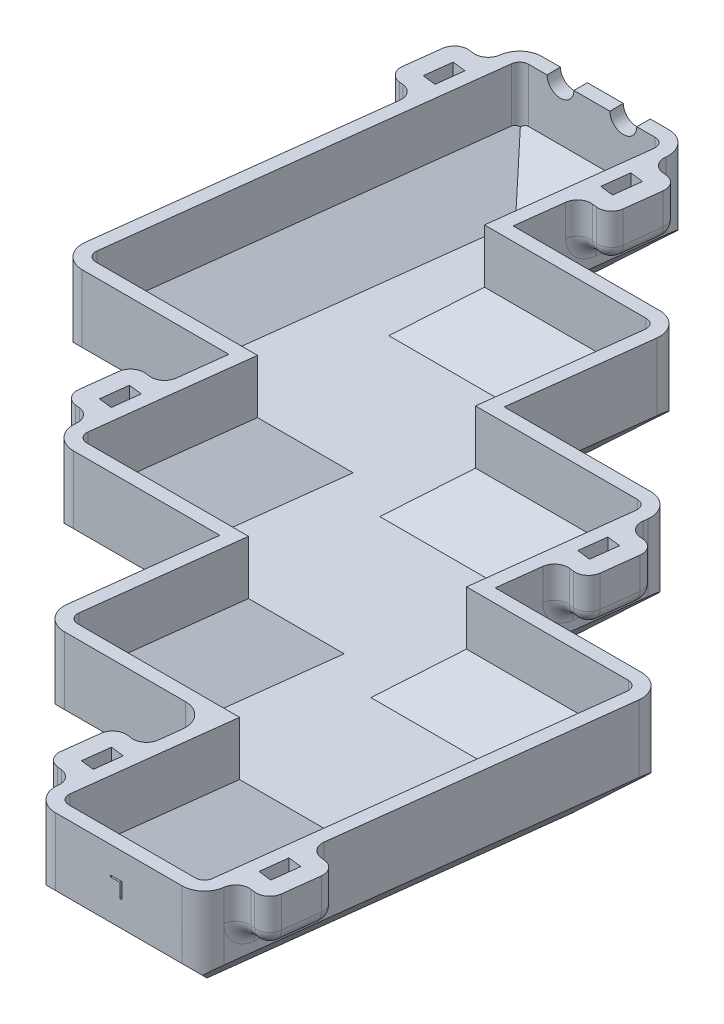
SolidWorks part; units mm, degrees
ref_plane "Front Plane" through (0, 0, 0) normal (0, 0, 1) x (1, 0, 0)
ref_plane "Top Plane" through (0, 0, 0) normal (0, 1, 0) x (1, 0, 0)
ref_plane "Right Plane" through (0, 0, 0) normal (1, 0, 0) x (0, 0, -1)
sketch "Sketch1" plane through (0, 0, 0) normal (0, 1, 0) x (1, 0, 0)
  line L12 (-13.5006, 46.1566) -> (24.7822, 46.1566)
  line L17 (-13.5006, 46.1566) -> (-24.7822, -46.1566)
  line L18 (24.7822, 46.1566) -> (13.5006, -46.1566)
  line L19 (-24.7822, -46.1566) -> (13.5006, -46.1566)
  line L20 (5.6408, 46.1566) -> (-5.6408, -46.1566) construction
  line L21 (47.3965, -82.0522) -> (9.1138, -82.0522)
  line L22 (47.3965, -82.0522) -> (58.6781, 10.261)
  line L23 (9.1138, -82.0522) -> (20.3954, 10.261)
  line L24 (58.6781, 10.261) -> (20.3954, 10.261)
  line L25 (28.2551, -82.0522) -> (39.5367, 10.261) construction
  line L26 (-47.3965, 82.0522) -> (-9.1138, 82.0522)
  line L27 (-47.3965, 82.0522) -> (-58.6781, -10.261)
  line L28 (-9.1138, 82.0522) -> (-20.3954, -10.261)
  line L29 (-58.6781, -10.261) -> (-20.3954, -10.261)
  line L30 (-28.2551, 82.0522) -> (-39.5367, -10.261) construction
  line L31 (-21.3932, -43.1566) -> (10.8449, -43.1566) construction
  line L32 (-21.3932, -43.1566) -> (-10.8449, 43.1566) construction
  line L33 (10.8449, -43.1566) -> (21.3932, 43.1566)
  line L34 (-10.8449, 43.1566) -> (21.3932, 43.1566) construction
  line L35 (5.2742, 43.1566) -> (21.156, 41.2157) construction
  line L36 (-20.3954, -10.261) -> (20.3954, 10.261) construction
  line L37 (92.574, -25.6346) -> (54.2913, -25.6346)
  line L38 (92.574, -25.6346) -> (81.2924, -117.9478)
  line L39 (54.2913, -25.6346) -> (43.0097, -117.9478)
  line L40 (81.2924, -117.9478) -> (43.0097, -117.9478)
  line L41 (13.5006, -46.1566) -> (54.2913, -25.6346) construction
  point P7 (0, 0)
  point P20 (5.2742, 43.1566)
  point P21 (-5.2742, -43.1566)
  point P26 (16.119, 0)
  point P28 (0, 0)
  point P30 (33.8959, -35.8956)
  point P36 (33.8959, -35.8956)
  dimension "D1" = 93
  dimension "D2" = 32
  dimension "D3" = 85
  dimension "D4" = 3
  dimension "D5" = 3
  dimension "D6" = 200
extrude "Boss-Extrude1" add sketch "Sketch1" along normal blind 25
sketch "Sketch4" plane through (0, 25, 0) normal (0, 1, 0) x (1, 0, 0)
  line L0 (-21.3932, -43.1566) -> (10.8449, -43.1566)
  line L1 (-21.3932, -43.1566) -> (-10.8449, 43.1566)
  line L2 (10.8449, -43.1566) -> (21.3932, 43.1566)
  line L3 (-10.8449, 43.1566) -> (21.3932, 43.1566)
  line L4 (12.5027, -79.0522) -> (44.7408, -79.0522)
  line L5 (12.5027, -79.0522) -> (23.051, 7.261)
  line L6 (44.7408, -79.0522) -> (55.2891, 7.261)
  line L7 (23.051, 7.261) -> (55.2891, 7.261)
  line L8 (39.1701, 7.261) -> (28.6217, -79.0522) construction
  line L9 (-44.7408, 79.0522) -> (-12.5027, 79.0522)
  line L10 (-44.7408, 79.0522) -> (-55.2891, -7.261)
  line L11 (-12.5027, 79.0522) -> (-23.051, -7.261)
  line L12 (-55.2891, -7.261) -> (-23.051, -7.261)
  line L13 (-28.6217, 79.0522) -> (-39.1701, -7.261) construction
  line L14 (-47.3965, 82.0522) -> (-9.1138, 82.0522) construction
  line L15 (-47.3965, 82.0522) -> (-58.6781, -10.261) construction
  line L16 (58.6781, 10.261) -> (20.3954, 10.261) construction
  line L17 (9.1138, -82.0522) -> (20.3954, 10.261) construction
  line L18 (-12.5027, 79.0522) -> (-6.4581, 79.0522)
  line L19 (-21.3932, -43.1566) -> (-27.4378, -43.1566)
  line L20 (12.5027, -79.0522) -> (6.4581, -79.0522)
  line L21 (21.3932, 43.1566) -> (27.4378, 43.1566)
  line L22 (-10.8449, 43.1566) -> (-16.8895, 43.1566)
  line L23 (-23.051, -7.261) -> (-17.0064, -7.261)
  line L24 (10.8449, -43.1566) -> (16.8895, -43.1566)
  line L25 (23.051, 7.261) -> (17.0064, 7.261)
  line L26 (56.947, -28.6346) -> (89.185, -28.6346)
  line L27 (56.947, -28.6346) -> (46.3986, -114.9478)
  line L28 (89.185, -28.6346) -> (78.6367, -114.9478)
  line L29 (46.3986, -114.9478) -> (78.6367, -114.9478)
  line L30 (56.947, -28.6346) -> (50.9023, -28.6346)
  line L31 (44.7408, -79.0522) -> (50.7854, -79.0522)
  line L32 (92.574, -25.6346) -> (81.2924, -117.9478) construction
  line L33 (92.574, -25.6346) -> (54.2913, -25.6346) construction
  dimension "D1" = 3
  dimension "D2" = 3
  dimension "D3" = 3
  dimension "D4" = 3
  dimension "D5" = 3
  dimension "D6" = 3
extrude "Cut-Extrude1" cut sketch "Sketch4" against normal blind 22 contours L10 L12 L11 L9 | L19 L1 L18 L11 | L3 L1 L0 L2 | L7 L5 L4 L6 | L21 L2 L20 L5 | L27 L29 L28 L26 | L6 L31 L27 L30
chamfer "Chamfer2" distance 10 angle 45 32 edges at (39.5367, 0, -10.261) (22.5888, 0, -28.2088) (5.6408, 0, -46.1566) (-11.3072, 0, -64.1044) (-28.2551, 0, -82.0522) (-53.0373, 0, -35.8956) (-39.5367, 0, 10.261) (-22.5888, 0, 28.2088) (-5.6408, 0, 46.1566) (11.3072, 0, 64.1044) (28.2551, 0, 82.0522) (45.2031, 0, 100) (56.4847, 0, 7.6868) (-28.6217, 3, -79.0522) (-14.6961, 3, -61.1044) (2.2518, 3, -43.1566) (19.1998, 3, -25.2088) (36.1478, 3, -7.261) (53.0957, 3, 10.6868) (31.6441, 3, 79.0522) (14.6961, 3, 61.1044) (-2.2518, 3, 43.1566) (-19.1998, 3, 25.2088) (-36.1478, 3, 7.261) (-50.015, 3, -35.8956) (62.151, 0, 117.9478) (86.9332, 0, 71.7912) (73.4326, 0, 25.6346) (70.0437, 3, 28.6346) (83.9109, 3, 71.7912) (62.5177, 3, 114.9478) (48.592, 3, 97)
fillet "Fillet4" radius 5 11 edges at (47.3965, 17.5, 82.0522) (9.1138, 17.5, 82.0522) (-24.7822, 17.5, 46.1566) (-58.6781, 17.5, 10.261) (-47.3965, 17.5, -82.0522) (-9.1138, 17.5, -82.0522) (24.7822, 17.5, -46.1566) (58.6781, 17.5, -10.261) (92.574, 17.5, 25.6346) (81.2924, 17.5, 117.9478) (43.0097, 17.5, 117.9478)
fillet "Fillet5" radius 2 10 edges at (-12.5027, 19, -79.0522) (12.5027, 19, 79.0522) (55.2891, 19, -7.261) (21.3932, 19, -43.1566) (-21.3932, 19, 43.1566) (-55.2891, 19, 7.261) (-44.7408, 19, -79.0522) (78.6367, 19, 114.9478) (46.3986, 19, 114.9478) (89.185, 19, 28.6346)
sketch "Sketch13" plane through (56.5791, 0, 6.9145) normal (-0.9926, 0, -0.1213) x (-0.1213, 0, 0.9926)
  line L5 (106.2111, 10) -> (106.2111, 25) construction
  line L6 (89.2111, 15) -> (103.2111, 15)
  line L8 (89.2111, 15) -> (89.2111, 25)
  line L10 (89.2111, 25) -> (103.2111, 25)
  line L11 (103.2111, 15) -> (103.2111, 25)
  line L16 (89.2111, 15) -> (103.2111, 25) construction
  line L17 (89.2111, 25) -> (103.2111, 15) construction
  line L18 (106.2111, 25) -> (81.3449, 25) construction
  point P0 (96.2111, 20)
  dimension "D1" = 10
  dimension "D2" = 14
  dimension "D3" = 3
extrude "Boss-Extrude7" add sketch "Sketch13" along normal blind 7
sketch "Sketch14" plane through (-56.5791, 0, -6.9145) normal (-0.9926, 0, -0.1213) x (-0.1213, 0, 0.9926)
  line L0 (-71.2705, 25) -> (11.6551, 25) construction
  line L5 (-54.2705, 15) -> (-68.2705, 15)
  line L6 (-54.2705, 15) -> (-54.2705, 25)
  line L7 (-54.2705, 25) -> (-68.2705, 25)
  line L8 (-68.2705, 15) -> (-68.2705, 25)
  line L9 (-54.2705, 15) -> (-68.2705, 25) construction
  line L10 (-54.2705, 25) -> (-68.2705, 15) construction
  line L11 (-71.2705, 25) -> (-71.2705, 10) construction
  line L12 (-29.8077, 25) -> (-29.8077, 10) construction
  line L13 (-71.2705, 10) -> (11.6551, 10) construction
  point P0 (-61.2705, 20)
  dimension "D1" = 3
  dimension "D2" = 14
  dimension "D3" = 10
extrude "Boss-Extrude8" add sketch "Sketch14" along normal blind 7
sketch "Sketch16" plane through (-18.8597, 0, -2.3048) normal (0.9926, 0, 0.1213) x (0.1213, 0, -0.9926)
  line L0 (74.6924, 25) -> (44.178, 25) construction
  line L1 (71.6924, 15) -> (57.6924, 15)
  line L2 (71.6924, 15) -> (71.6924, 25)
  line L3 (71.6924, 25) -> (57.6924, 25)
  line L4 (57.6924, 15) -> (57.6924, 25)
  line L5 (71.6924, 15) -> (57.6924, 25) construction
  line L6 (71.6924, 25) -> (57.6924, 15) construction
  line L7 (74.6924, 10) -> (74.6924, 25) construction
  point P0 (64.6924, 20)
  dimension "D1" = 3
  dimension "D2" = 14
  dimension "D3" = 10
extrude "Boss-Extrude10" add sketch "Sketch16" along normal blind 7
sketch "Sketch22" plane through (94.2984, 0, 11.5242) normal (0.9926, 0, 0.1213) x (0.1213, 0, -0.9926)
  line L0 (-61.3264, 25) -> (-61.3264, 10) construction
  line L1 (-19.8636, 25) -> (-102.7892, 25) construction
  line L2 (-102.7892, 10) -> (-19.8636, 10) construction
  line L3 (-102.7892, 25) -> (-102.7892, 10) construction
  line L4 (-85.7892, 15) -> (-99.7892, 15)
  line L5 (-85.7892, 15) -> (-85.7892, 25)
  line L6 (-85.7892, 25) -> (-99.7892, 25)
  line L7 (-99.7892, 15) -> (-99.7892, 25)
  line L8 (-85.7892, 15) -> (-99.7892, 25) construction
  line L9 (-85.7892, 25) -> (-99.7892, 15) construction
  point P6 (-92.7892, 20)
  dimension "D1" = 3
  dimension "D2" = 14
  dimension "D3" = 10
extrude "Boss-Extrude12" add sketch "Sketch22" along normal blind 7
sketch "Sketch25" plane through (-18.8597, 0, -2.3048) normal (-0.9926, 0, -0.1213) x (-0.1213, 0, 0.9926)
  line L0 (12.6593, 25) -> (43.1737, 25) construction
  line L1 (26.1737, 15) -> (40.1737, 15)
  line L2 (26.1737, 15) -> (26.1737, 25)
  line L3 (26.1737, 25) -> (40.1737, 25)
  line L4 (40.1737, 15) -> (40.1737, 25)
  line L5 (26.1737, 15) -> (40.1737, 25) construction
  line L6 (26.1737, 25) -> (40.1737, 15) construction
  line L7 (43.1737, 10) -> (43.1737, 25) construction
  point P0 (33.1737, 20)
  dimension "D1" = 3
  dimension "D2" = 14
  dimension "D3" = 10
extrude "Boss-Extrude13" add sketch "Sketch25" along normal blind 7
sketch "Sketch26" plane through (56.5791, 0, 6.9145) normal (0.9926, 0, 0.1213) x (0.1213, 0, -0.9926)
  line L0 (-18.8594, 25) -> (11.6551, 25) construction
  line L1 (-6.3449, 15) -> (7.6551, 15)
  line L2 (-6.3449, 15) -> (-6.3449, 25)
  line L3 (-6.3449, 25) -> (7.6551, 25)
  line L4 (7.6551, 15) -> (7.6551, 25)
  line L5 (11.6551, 10) -> (11.6551, 25) construction
  dimension "D1" = 4
  dimension "D2" = 14
  dimension "D3" = 10
extrude "Boss-Extrude14" add sketch "Sketch26" along normal blind 7
sketch "Sketch23" plane through (0, 25, 0) normal (0, 1, 0) x (1, 0, 0)
  line L0 (-51.7604, 71.0744) -> (-48.7826, 70.7104)
  line L1 (-51.7604, 71.0744) -> (-52.4882, 65.1187)
  line L2 (-48.7826, 70.7104) -> (-49.5104, 64.7547)
  line L3 (-52.4882, 65.1187) -> (-49.5104, 64.7547)
  line L4 (-55.2456, 75.53) -> (-48.2973, 74.6809) construction
  line L5 (-49.9956, 60.7843) -> (-57.9929, -4.6545) construction
  line L12 (-10.6481, 69.4974) -> (-7.6702, 69.1334)
  line L13 (-10.6481, 69.4974) -> (-11.3759, 63.5417)
  line L14 (-7.6702, 69.1334) -> (-8.3981, 63.1777)
  line L15 (-11.3759, 63.5417) -> (-8.3981, 63.1777)
  line L17 (-3.2146, 72.6187) -> (-10.1629, 73.4678) construction
  line L18 (-9.7989, 76.4457) -> (-10.1629, 73.4678) construction
  line L23 (-25.4978, -27.2821) -> (-22.52, -27.6461)
  line L24 (-25.4978, -27.2821) -> (-26.2257, -33.2378)
  line L30 (83.4063, -100.6503) -> (86.3842, -101.0143)
  line L37 (42.294, -99.0733) -> (45.2718, -99.4373)
  line L38 (42.294, -99.0733) -> (41.5662, -105.029)
  line L39 (45.2718, -99.4373) -> (44.544, -105.393)
  line L40 (41.5662, -105.029) -> (44.544, -105.393)
  line L43 (38.8088, -94.6177) -> (45.7571, -95.4668) construction
  line L44 (45.7571, -95.4668) -> (46.7113, -87.6587) construction
  line L49 (-22.52, -27.6461) -> (-23.2478, -33.6018)
  line L50 (-26.2257, -33.2378) -> (-23.2478, -33.6018)
  line L53 (-28.9831, -22.8265) -> (-22.0348, -23.6756) construction
  line L54 (-20.3954, -10.261) -> (-22.0348, -23.6756) construction
  line L55 (57.0224, -3.2865) -> (60.0003, -3.6504)
  line L56 (57.0224, -3.2865) -> (56.2946, -9.2422)
  line L57 (60.0003, -3.6504) -> (59.2724, -9.6061)
  line L58 (56.2946, -9.2422) -> (59.2724, -9.6061)
  line L59 (57.5077, 0.684) -> (57.9929, 4.6545) construction
  line L60 (64.456, -0.1652) -> (57.5077, 0.684) construction
  line L61 (83.4063, -100.6503) -> (82.6785, -106.606)
  line L62 (86.3842, -101.0143) -> (85.6563, -106.97)
  line L63 (82.6785, -106.606) -> (85.6563, -106.97)
  line L64 (90.8399, -97.529) -> (83.8915, -96.6799) construction
  line L65 (91.8888, -31.2411) -> (83.8915, -96.6799) construction
  dimension "D1" = 6
  dimension "D2" = 3
  dimension "D3" = 4
  dimension "D4" = 6
  dimension "D5" = 4
  dimension "D6" = 3
  dimension "D7" = 4
  dimension "D8" = 6
  dimension "D9" = 3
  dimension "D10" = 4
  dimension "D11" = 3
  dimension "D12" = 6
  dimension "D13" = 3
  dimension "D14" = 6
  dimension "D15" = 4
  dimension "D16" = 4
  dimension "D17" = 3
  dimension "D18" = 6
extrude "Cut-Extrude2" cut sketch "Sketch23" against normal through all
fillet "Fillet6" radius 3 54 edges at (90.8399, 20, 97.529) (89.9907, 15, 104.4773) (89.1415, 20, 111.4256) (-10.1629, 20, -73.4678) (-11.8612, 20, -59.5712) (-48.2973, 20, -74.6809) (-49.753, 15, -62.7695) (-23.4904, 15, 35.587) (45.7571, 20, 95.4668) (44.0588, 20, 109.3634) (83.6489, 15, 98.6651) (82.4359, 15, 108.5913) (-3.2146, 20, -72.6187) (-6.6887, 15, -73.0432) (-10.4055, 15, -71.4826) (-11.6185, 15, -61.5564) (-4.0637, 15, -65.6704) (-8.387, 15, -59.1466) (-4.9129, 20, -58.7221) (-55.2456, 20, -75.53) (-51.7715, 15, -75.1055) (-48.5399, 15, -72.6957) (-49.9956, 20, -60.7843) (-56.9439, 20, -61.6334) (-56.0948, 15, -68.5817) (-53.4698, 15, -61.2089) (-28.9831, 20, 22.8265) (-25.5089, 15, 23.251) (-22.0348, 20, 23.6756) (-22.2774, 15, 25.6608) (-23.7331, 20, 37.5722) (-29.8322, 15, 29.7748) (-30.6814, 20, 36.7231) (-27.2072, 15, 37.1476) (38.8088, 20, 94.6177) (42.2829, 15, 95.0422) (45.5145, 15, 97.452) (44.3014, 15, 107.3782) (37.9596, 15, 101.566) (37.1105, 20, 108.5143) (40.5846, 15, 108.9388) (83.8915, 20, 96.6799) (85.6674, 15, 111.0011) (82.1932, 20, 110.5765) (87.3657, 15, 97.1045) (55.8094, 20, 13.2126) (57.2651, 15, 1.3012) (56.052, 15, 11.2274) (59.2835, 15, 13.6372) (62.7577, 20, 14.0618) (63.6068, 15, 7.1135) (60.9818, 15, -0.2594) (57.5077, 20, -0.684) (64.456, 20, 0.1652)
sketch "Sketch27" plane through (0, 0, 117.9478) normal (0, 0, 1) x (1, 0, 0)
  line L0 (62.7621, 25) -> (62.7621, 10) construction
  line L1 (76.8662, 25) -> (48.6579, 25) construction
  line L2 (48.6579, 10) -> (76.8662, 10) construction
  text T0 "<r180>L</r>" font "Century Gothic" height 3.5
  text T1 "<r180>L</r>" font "Century Gothic" height 3.5
  text T2 "<r180>L</r>" font "Century Gothic" height 3.5
  point P7 (61.4724, 28.629)
  point P8 (65.217, 19.8667)
  point P9 (64.113, 19.6703)
  point P10 (0, 0)
  point P11 (0, 0)
  point P12 (63.7543, 18.7671)
  point P13 (0, 0)
  point P16 (64.1352, 19.1038)
extrude "Cut-Extrude3" cut sketch "Sketch27" against normal blind 1
sketch "Sketch28" plane through (0, 0, -82.0522) normal (0, 0, -1) x (-1, 0, 0)
  line L0 (42.9703, 25) -> (14.762, 25) construction
  line L1 (28.8662, 25) -> (28.8662, 26.1009) construction
  circle A0 centre (35.8662, 25) radius 3
  circle A1 centre (21.8662, 25) radius 3
  dimension "D1" = 6
  dimension "D2" = 7
extrude "Cut-Extrude4" cut sketch "Sketch28" against normal blind 10
